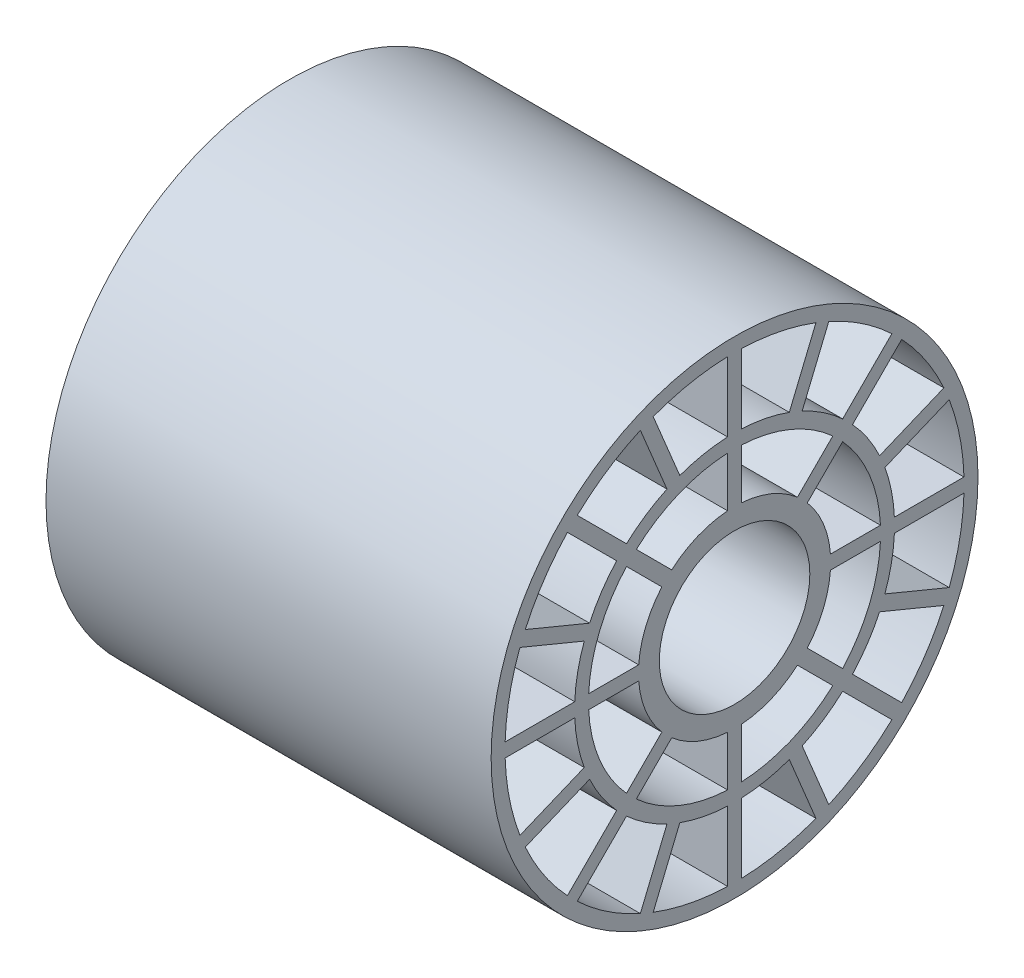
SolidWorks part; units mm, degrees
note: The reader was unsure of these and kept them because the rebuilt part matched: shared geometry of "Sketch1<3>", "Sketch1<5>".
material "PPE"
ref_plane "Front" through (0, 0, 0) normal (0, 0, 1) x (1, 0, 0)
ref_plane "Top" through (0, 0, 0) normal (0, 1, 0) x (1, 0, 0)
ref_plane "Right" through (0, 0, 0) normal (1, 0, 0) x (0, 0, -1)
sketch "Sketch1" plane through (0, 0, 0) normal (1, 0, 0) x (0, 0, -1)
  circle A0 centre (0, 0) radius 22.225
  circle A1 centre (0, 0) radius 6.8707
  circle A2 centre (0, 0) radius 14.605
  dimension "D1" = 44.45
  dimension "D2" = 13.7414
  dimension "D3" = 29.21
extrude "Extrude-Thin1" add sketch "Sketch1" along normal mid plane 40.64 thin contours A0 | A2
extrude "Extrude-Thin2" add sketch "Sketch1<3>" along normal mid plane 40.64 separate body thin contours A1
sketch "Sketch1<3>" plane through (0, 0, 0) normal (1, 0, 0) x (0, 0, -1) same geometry as "Sketch1"
sketch "Sketch2" plane through (0, 0, 0) normal (1, 0, 0) x (0, 0, -1)
  line L0 (0, 20.955) -> (0, -20.955)
  line L1 (-20.955, 0) -> (20.955, 0)
  line L2 (-14.8174, -14.8174) -> (14.8174, 14.8174)
  line L4 (-14.8174, 14.8174) -> (14.8174, -14.8174)
  circle A2 centre (0, 0) radius 20.955
  circle A3 centre (0, 0) radius 20.955 construction
  dimension "D1" = 45
  dimension "D2" = 45
extrude "Extrude-Thin3" add sketch "Sketch2" along normal mid plane 40.64 thin
extrude "Cut-Extrude1" cut sketch "Sketch1<5>" against normal mid plane 40.64 contours A1
sketch "Sketch1<5>" plane through (0, 0, 0) normal (1, 0, 0) x (0, 0, -1) same geometry as "Sketch1"
sketch "Sketch4" plane through (0, 0, 0) normal (1, 0, 0) x (0, 0, -1)
  line L0 (-8.0191, 19.3599) -> (-5.3947, 13.0239)
  line L1 (0, 20.955) -> (0, -20.955) construction
  circle A0 centre (0, 0) radius 14.605 construction
  circle A1 centre (0, 0) radius 20.955 construction
  point P0 (-5.5891, 13.4933)
  point P1 (-23.9244, 18.361)
  dimension "D1" = 22.5
  dimension "D2" = 0.508
extrude "Extrude-Thin6" add sketch "Sketch4" along normal mid plane 40.64 thin contours L0 thin type mid plane wall 1.27
pattern_circular "CirPattern1" count 8 over 360 about axis through (0, 0, 0) along (1, 0, 0) of "Extrude-Thin6"
equation "\"D2@Sketch2\"=\"D1@Sketch2\""
